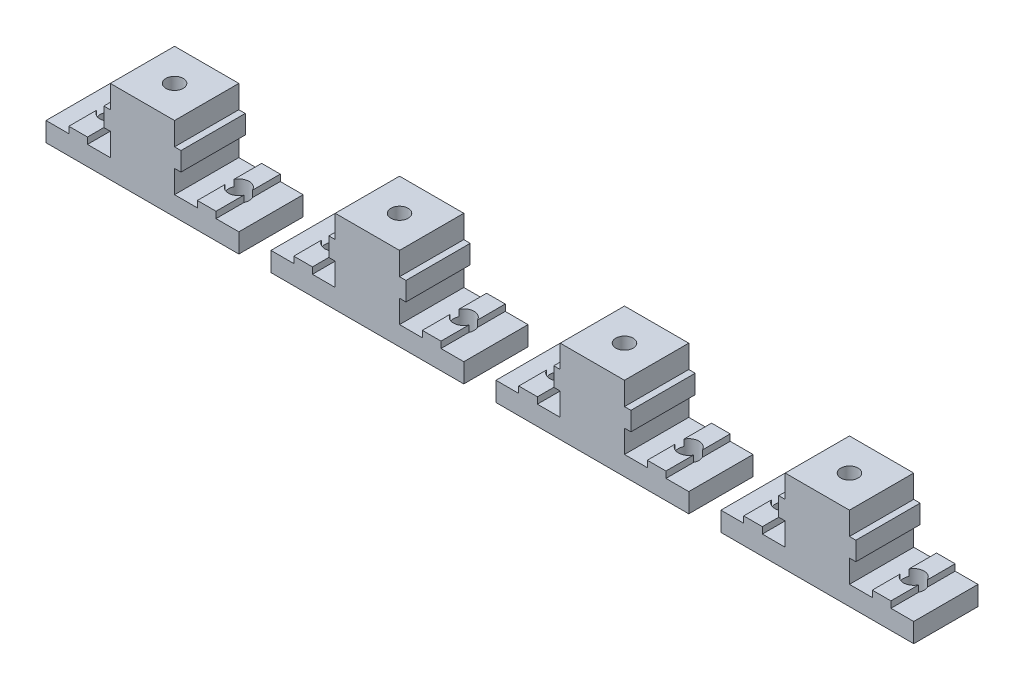
SolidWorks part; units mm, degrees
ref_plane "Front Plane" through (0, 0, 0) normal (0, 0, 1) x (1, 0, 0)
ref_plane "Top Plane" through (0, 0, 0) normal (0, 1, 0) x (1, 0, 0)
ref_plane "Right Plane" through (0, 0, 0) normal (1, 0, 0) x (0, 0, -1)
sketch "Esquisse1" plane through (0, 0, 0) normal (0, 0, 1) x (1, 0, 0)
  line L0 (-15, 0) -> (-15, 3)
  line L1 (-15, 3) -> (-11.45, 3)
  line L2 (-11.45, 3) -> (-11.45, 4)
  line L3 (-11.45, 4) -> (-8.55, 4)
  line L4 (-8.55, 4) -> (-8.55, 3)
  line L5 (-8.55, 3) -> (-5, 3)
  line L6 (-5, 3) -> (-5, 6.55)
  line L7 (0, 0) -> (-15, 0)
  line L8 (-5, 6.55) -> (-6, 6.55)
  line L9 (-6, 6.55) -> (-6, 9.45)
  line L10 (-6, 9.45) -> (-5, 9.45)
  line L11 (-5, 9.45) -> (-5, 13)
  line L12 (-5, 13) -> (0, 13)
  line L13 (0, 13) -> (0, 0)
  dimension "D1" = 15
  dimension "D2" = 3
  dimension "D3" = 1
  dimension "D4" = 2.9
  dimension "D5" = 3.55
  dimension "D6" = 5
  dimension "D7" = 10
  dimension "D8" = 2.9
  dimension "D9" = 3.55
extrude "Main" add sketch "Esquisse1" along normal blind 10
sketch "Esquisse2" plane through (0, 4, 0) normal (0, 1, 0) x (1, 0, 0)
  line L2 (-11.45, -10) -> (-15, -10) construction
  line L4 (-8.55, 0) -> (-11.45, 0) construction
  circle A1 centre (-10, -5) radius 1.6
  point P12 (-10, 0)
  dimension "D2" = 5
  dimension "D3" = 3.2
  dimension "D1" = 5
extrude "TopHole" cut sketch "Esquisse2" against normal through all
ref_axis "Axe1" through (-5.5, 0, 0) along (1, 0, 0)
mirror "Symétrie1" about plane through (0, 0, 0) normal (1, 0, 0) of "Main", "TopHole"
sketch "Esquisse3" plane through (0, 13, 0) normal (0, 1, 0) x (1, 0, 0)
  line L0 (0, -2.2) -> (0, 2.2) construction
  line L2 (5, -10) -> (-5, -10) construction
  circle A1 centre (0, -5) radius 1.35
  dimension "D1" = 2.7
  dimension "D2" = 5
extrude "Enlèv. mat.-Extru.2" cut sketch "Esquisse3" against normal through all
ref_axis "Axe2" through (16.5, 0, 0) along (-1, 0, 0)
pattern_linear "Répétition linéaire3" count 4 spacing 35 along (1, 0, 0) of bodies 108
